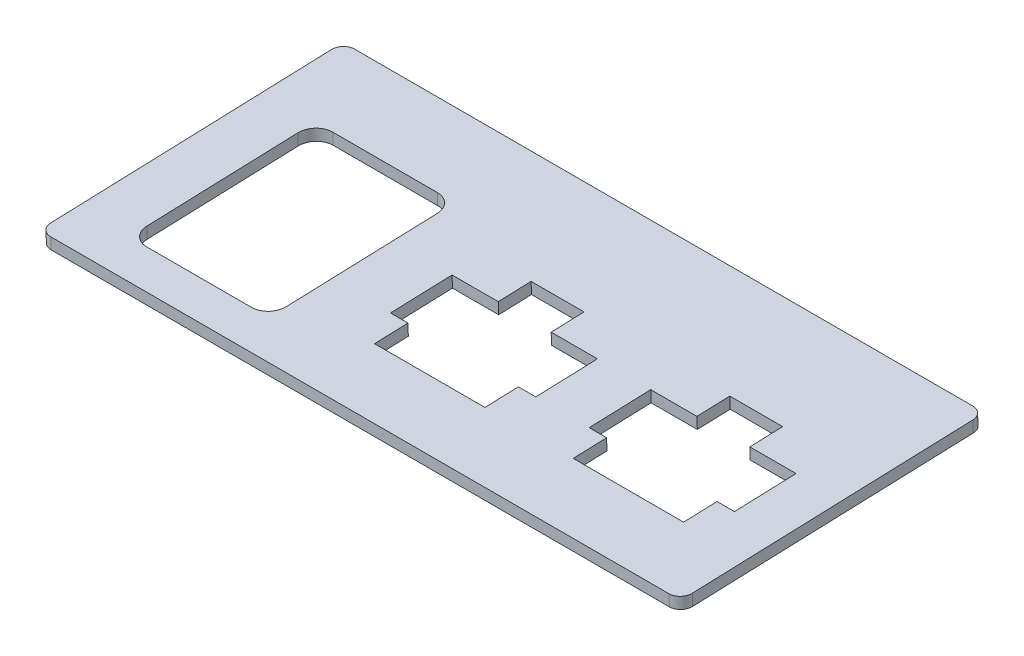
SolidWorks part; units mm, degrees
ref_plane "Front Plane" through (0, 0, 0) normal (0, 0, 1) x (1, 0, 0)
ref_plane "Top Plane" through (0, 0, 0) normal (0, 1, 0) x (1, 0, 0)
ref_plane "Right Plane" through (0, 0, 0) normal (1, 0, 0) x (0, 0, -1)
sketch "Sketch1" plane through (0, -71.9872, -2.5138) normal (0, 0.9994, 0.0349) x (1, 0, 0)
  line L0 (-56.175, 48.6398) -> (56.175, 48.6398) construction
  line L1 (-52.175, -2.9116) -> (-56.175, -2.9116) construction
  line L8 (-55.175, -4.4116) -> (55.175, -4.4116)
  line L9 (55.175, -4.4116) -> (55.175, 47.8898)
  line L10 (55.175, 47.8898) -> (-55.175, 47.8898)
  line L11 (-55.175, 47.8898) -> (-55.175, -4.4116)
  dimension "D4" = 0.75
  dimension "D1" = 1.5
  dimension "D2" = 3.0034
  dimension "D3" = 3.0034
extrude "Boss-Extrude1" add sketch "Sketch1" along normal blind 2
sketch "Sketch2" plane through (0, -71.9872, -2.5138) normal (0, -0.9994, -0.0349) x (1, 0, 0)
  line L0 (-4.05, -23.4641) -> (-4.05, -29.1141)
  line L1 (-43.175, -2.1141) -> (-25.175, -2.1141)
  line L2 (-46.175, -5.1141) -> (-46.175, -31.1141)
  line L3 (-43.175, -34.1141) -> (-25.175, -34.1141)
  line L4 (-22.175, -5.1141) -> (-22.175, -31.1141)
  line L5 (-12, -12.8641) -> (-9, -12.8641)
  line L6 (-12, -12.8641) -> (-12, -23.4641)
  line L7 (-12, -23.4641) -> (-4.05, -23.4641)
  line L8 (13, -12.8641) -> (13, -23.4641)
  line L9 (-9, -7.1141) -> (10, -7.1141)
  line L10 (-9, -7.1141) -> (-9, -12.8641)
  line L11 (-4.05, -29.1141) -> (5.05, -29.1141)
  line L12 (10, -7.1141) -> (10, -12.8641)
  line L13 (10, -12.8641) -> (13, -12.8641)
  line L14 (5.05, -23.4641) -> (5.05, -29.1141)
  line L15 (5.05, -23.4641) -> (13, -23.4641)
  line L16 (-13, -4.6141) -> (14, -31.6141) construction
  line L17 (-13, -4.6141) -> (14, -4.6141) construction
  line L18 (-13, -4.6141) -> (-13, -31.6141) construction
  line L19 (-13, -31.6141) -> (14, -31.6141) construction
  line L20 (14, -4.6141) -> (14, -31.6141) construction
  line L21 (17.5875, 3.7502) -> (17.5875, -36.664) construction
  line L22 (47.175, -18.1641) -> (22.175, -18.1641) construction
  line L23 (34.675, -7.1141) -> (34.675, -29.1141) construction
  line L24 (21.175, -4.6141) -> (21.175, -31.6141) construction
  line L25 (48.175, -31.6141) -> (21.175, -31.6141) construction
  line L26 (48.175, -4.6141) -> (48.175, -31.6141) construction
  line L27 (48.175, -4.6141) -> (21.175, -4.6141) construction
  line L28 (-48.175, -18.1141) -> (-46.175, -18.1141) construction
  line L29 (-48.175, -0.1141) -> (-20.175, -0.1141) construction
  line L30 (-48.175, -0.1141) -> (-48.175, -36.1141) construction
  line L31 (-48.175, -36.1141) -> (-20.175, -36.1141) construction
  line L32 (-20.175, -0.1141) -> (-20.175, -36.1141) construction
  line L33 (-34.175, -2.1141) -> (-34.175, -0.1141) construction
  line L34 (0.5, -7.1141) -> (0.5, -29.1141) construction
  line L35 (-12, -18.1641) -> (13, -18.1641) construction
  line L36 (48.175, -4.6141) -> (21.175, -31.6141) construction
  line L37 (30.125, -23.4641) -> (22.175, -23.4641)
  line L38 (30.125, -23.4641) -> (30.125, -29.1141)
  line L39 (25.175, -12.8641) -> (22.175, -12.8641)
  line L40 (25.175, -7.1141) -> (25.175, -12.8641)
  line L41 (39.225, -29.1141) -> (30.125, -29.1141)
  line L42 (44.175, -7.1141) -> (44.175, -12.8641)
  line L43 (44.175, -7.1141) -> (25.175, -7.1141)
  line L44 (22.175, -12.8641) -> (22.175, -23.4641)
  line L45 (47.175, -23.4641) -> (39.225, -23.4641)
  line L46 (47.175, -12.8641) -> (47.175, -23.4641)
  line L47 (47.175, -12.8641) -> (44.175, -12.8641)
  line L48 (39.225, -23.4641) -> (39.225, -29.1141)
  line L49 (21.175, -18.1141) -> (14, -18.1141) construction
  line L50 (-55.175, 4.4116) -> (55.175, 4.4116) construction
  line L51 (48.175, -18.1141) -> (52.175, -18.1141) construction
  line L52 (55.175, 4.4116) -> (55.175, -47.8898) construction
  line L53 (-46.7914, -40.6398) -> (46.7914, -40.6398) construction
  line L54 (-13, -18.1141) -> (-20.175, -18.1141) construction
  line L55 (-34.175, -0.1141) -> (-34.175, 4.4116) construction
  line L56 (-34.175, -36.1141) -> (-34.175, -40.6398) construction
  line L57 (-55.175, -47.8898) -> (-55.175, 4.4116) construction
  line L58 (-48.175, -18.1141) -> (-52.175, -18.1141) construction
  arc A0 (-46.175, -31.1141) -> (-43.175, -34.1141) centre (-43.175, -31.1141) ccw
  arc A1 (-25.175, -34.1141) -> (-22.175, -31.1141) centre (-25.175, -31.1141) ccw
  arc A2 (-25.175, -2.1141) -> (-22.175, -5.1141) centre (-25.175, -5.1141) cw
  arc A3 (-43.175, -2.1141) -> (-46.175, -5.1141) centre (-43.175, -5.1141) ccw
  point P28 (0.5, -18.1141)
  point P63 (34.675, -18.1141)
  dimension "D1" = 3
  dimension "D2" = 32
  dimension "D3" = 24
  dimension "D4" = 28
  dimension "D5" = 36
  dimension "D6" = 25
  dimension "D7" = 22
  dimension "D8" = 10.6
  dimension "D9" = 19
  dimension "D10" = 9.1
  dimension "D11" = 5.75
  dimension "D12" = 27
  dimension "D13" = 27
  dimension "D14" = 4
  dimension "D15" = 3
  dimension "D16" = 3
extrude "Cut-Extrude1" cut sketch "Sketch2" against normal up to next
fillet "Fillet1" radius 2 4 edges at (-55.175, -71.1418, 1.93) (55.175, -71.1418, 1.93) (55.175, -69.3165, -50.3395) (-55.175, -69.3165, -50.3395)
